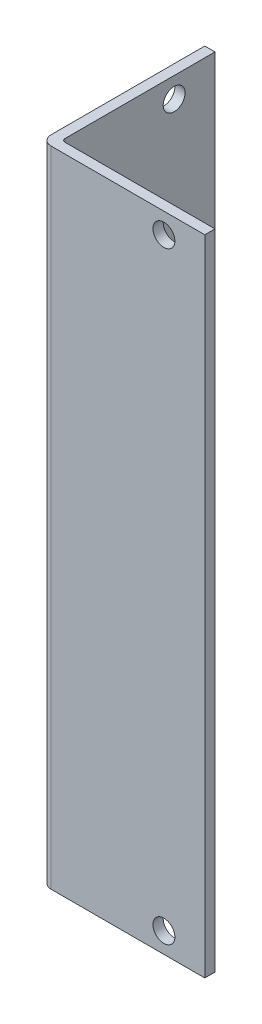
SolidWorks part; units mm, degrees
material "6061-T6 (SS)"
ref_plane "Front Plane" through (0, 0, 0) normal (0, 0, 1) x (1, 0, 0)
ref_plane "Top Plane" through (0, 0, 0) normal (0, 1, 0) x (1, 0, 0)
ref_plane "Right Plane" through (0, 0, 0) normal (1, 0, 0) x (0, 0, -1)
sketch "Sketch1" plane through (0, 0, 0) normal (0, 1, 0) x (1, 0, 0)
  line L1 (-12.7, -12.7) -> (12.7, -12.7)
  line L2 (-12.7, -12.7) -> (-12.7, 12.7)
  line L3 (-12.7, 12.7) -> (12.7, 12.7)
  line L4 (12.7, -12.7) -> (12.7, 12.7)
  line L5 (-12.7, -12.7) -> (12.7, 12.7) construction
  line L6 (-12.7, 12.7) -> (12.7, -12.7) construction
  point P0 (0, 0)
  dimension "D1" = 25.4
  dimension "D2" = 25.4
extrude "Boss-Extrude1" add sketch "Sketch1" along normal mid plane 113.5
sketch "Sketch2" plane through (0, 56.75, 0) normal (0, 1, 0) x (1, 0, 0)
  line L0 (-12.7, 12.7) -> (-12.7, -12.7) construction
  line L1 (12.7, 12.7) -> (-11.1125, 12.7)
  line L2 (12.7, 12.7) -> (12.7, -11.1125)
  line L3 (12.7, -11.1125) -> (-11.1125, -11.1125)
  line L4 (-11.1125, 12.7) -> (-11.1125, -11.1125)
  line L5 (-12.7, -12.7) -> (12.7, -12.7) construction
  dimension "D1" = 1.5875
  dimension "D2" = 1.5875
extrude "Cut-Extrude1" cut sketch "Sketch2" against normal through all
fillet "Fillet1" radius 0.508 1 edges at (-11.1125, 0, 11.1125)
hole_wizard "M3 Clearance Hole1" positions "Sketch3" profile "Sketch4" hole size "M3" standard "ANSI Metric" end condition through all
sketch "Sketch3" plane through (0, 0, 12.7) normal (0, 0, 1) x (1, 0, 0)
  line L1 (-12.7, 56.75) -> (12.7, 56.75) construction
  line L2 (12.7, 56.75) -> (12.7, -56.75) construction
  point P0 (6.35, 47.075)
  dimension "D1" = 6.35
  dimension "D2" = 9.675
sketch "Sketch4" plane through (6.35, 47.075, 12.7) normal (1, 0, 0) x (0, -1, 0)
  line L0 (0, 0) -> (0, 25.4)
  line L1 (0, 25.4) -> (1.7, 25.4)
  line L2 (1.7, 25.4) -> (1.7, 0)
  line L5 (1.7, 0) -> (0, 0)
  line L11 (0, -6.35) -> (0, 107.95) construction
  dimension "Thru Hole Dia." = 3.4
  dimension "Thru Hole Depth" = 25.4
hole_wizard "M3 Clearance Hole2" positions "Sketch5" profile "Sketch6" hole size "M3" standard "ANSI Metric" end condition through all
sketch "Sketch5" plane through (-12.7, 0, 0) normal (-1, 0, 0) x (0, 0, 1)
  line L1 (-12.7, 56.75) -> (12.7, 56.75) construction
  line L2 (-12.7, 56.75) -> (-12.7, -56.75) construction
  point P0 (-6.35, 47.075)
  dimension "D1" = 6.35
  dimension "D2" = 9.675
sketch "Sketch6" plane through (-12.7, 47.075, -6.35) normal (0, 1, 0) x (0, 0, 1)
  line L0 (0, 0) -> (0, 25.4)
  line L1 (0, 25.4) -> (1.7, 25.4)
  line L2 (1.7, 25.4) -> (1.7, 0)
  line L5 (1.7, 0) -> (0, 0)
  line L11 (0, -6.35) -> (0, 107.95) construction
  dimension "Thru Hole Dia." = 3.4
  dimension "Thru Hole Depth" = 25.4
hole_wizard "M3 Clearance Hole3" positions "Sketch7" profile "Sketch8" hole size "M3" standard "ANSI Metric" end condition through all
sketch "Sketch7" plane through (0, 0, 12.7) normal (0, 0, 1) x (1, 0, 0)
  line L2 (-12.7, -56.75) -> (12.7, -56.75) construction
  line L3 (12.7, 56.75) -> (12.7, -56.75) construction
  point P0 (6.35, -46.575)
  dimension "D1" = 6.35
  dimension "D2" = 10.175
sketch "Sketch8" plane through (6.35, -46.575, 12.7) normal (1, 0, 0) x (0, -1, 0)
  line L0 (0, 0) -> (0, 25.4)
  line L1 (0, 25.4) -> (1.7, 25.4)
  line L2 (1.7, 25.4) -> (1.7, 0)
  line L5 (1.7, 0) -> (0, 0)
  line L11 (0, -6.35) -> (0, 107.95) construction
  dimension "Thru Hole Dia." = 3.4
  dimension "Thru Hole Depth" = 25.4
hole_wizard "M3 Clearance Hole4" positions "Sketch9" profile "Sketch10" hole size "M3" standard "ANSI Metric" end condition through all
sketch "Sketch9" plane through (-12.7, 0, 0) normal (-1, 0, 0) x (0, 0, 1)
  line L1 (-12.7, -56.75) -> (12.7, -56.75) construction
  line L2 (-12.7, 56.75) -> (-12.7, -56.75) construction
  point P0 (-6.35, -46.575)
  dimension "D1" = 6.35
  dimension "D2" = 10.175
sketch "Sketch10" plane through (-12.7, -46.575, -6.35) normal (0, 1, 0) x (0, 0, 1)
  line L0 (0, 0) -> (0, 25.4)
  line L1 (0, 25.4) -> (1.7, 25.4)
  line L2 (1.7, 25.4) -> (1.7, 0)
  line L5 (1.7, 0) -> (0, 0)
  line L11 (0, -6.35) -> (0, 107.95) construction
  dimension "Thru Hole Dia." = 3.4
  dimension "Thru Hole Depth" = 25.4
fillet "Fillet2" radius 1.5 1 edges at (-12.7, 0, 12.7)
sketch "Sketch11" plane through (-12.7, 0, 0) normal (-1, 0, 0) x (0, 0, 1)
  line L0 (12.7, 56.75) -> (12.7, -56.75) construction
  line L1 (-12.7, 56.75) -> (4.2, 56.75)
  line L2 (-12.7, 56.75) -> (-12.7, 50.25)
  line L3 (-12.7, 50.25) -> (4.2, 50.25)
  line L4 (4.2, 56.75) -> (4.2, 50.25)
  line L6 (-12.7, -56.75) -> (4.2, -56.75)
  line L7 (-12.7, -56.75) -> (-12.7, -49.75)
  line L8 (-12.7, -49.75) -> (4.2, -49.75)
  line L9 (4.2, -56.75) -> (4.2, -49.75)
  dimension "D1" = 8.5
  dimension "D2" = 6.5
  dimension "D3" = 7
extrude "Cut-Extrude2" cut sketch "Sketch11" against normal up to next
sketch "Sketch12" plane through (0, 0, 12.7) normal (0, 0, 1) x (1, 0, 0)
  line L0 (-12.7, -56.75) -> (-12.7, 56.75) construction
  line L1 (12.7, 56.75) -> (-4.2, 56.75)
  line L2 (12.7, 56.75) -> (12.7, 50.25)
  line L3 (12.7, 50.25) -> (-4.2, 50.25)
  line L4 (-4.2, 56.75) -> (-4.2, 50.25)
  line L5 (12.7, -56.75) -> (-4.2, -56.75)
  line L6 (12.7, -56.75) -> (12.7, -49.75)
  line L7 (12.7, -49.75) -> (-4.2, -49.75)
  line L8 (-4.2, -56.75) -> (-4.2, -49.75)
  dimension "D1" = 8.5
  dimension "D2" = 7
  dimension "D3" = 8.5
  dimension "D4" = 6.5
extrude "Cut-Extrude3" cut sketch "Sketch12" against normal up to next
fillet "Fillet3" radius 3.81 4 edges at (-4.2, -49.75, 11.9062) (-11.9063, -49.75, 4.2) (-11.9063, 50.25, 4.2) (-4.2, 50.25, 11.9062)
sketch "Sketch13" plane through (-12.7, 0, 0) normal (-1, 0, 0) x (0, 0, 1)
  line L0 (4.2, -56.75) -> (4.2, 56.75) construction
  line L9 (2.7, -56.75) -> (2.7, 56.75) construction
  line L10 (-12.7, 50.25) -> (-12.7, -49.75) construction
  line L11 (2.7, -43.4) -> (-12.7, -43.4)
  line L12 (2.7, -43.4) -> (2.7, 43.9)
  line L13 (2.7, 43.9) -> (-12.7, 43.9)
  line L14 (-12.7, -43.4) -> (-12.7, 43.9)
  circle A2 centre (-6.35, 47.075) radius 1.7 construction
  circle A3 centre (-6.35, -46.575) radius 1.7 construction
  dimension "D2" = 3.175
  dimension "D3" = 3.175
  dimension "D1" = 1.5
extrude "Cut-Extrude4" cut sketch "Sketch13" against normal up to next
sketch "Sketch14" plane through (0, 0, 12.7) normal (0, 0, 1) x (1, 0, 0)
  line L0 (-4.2, 56.75) -> (-4.2, -56.75) construction
  line L1 (-2.7, 56.75) -> (-2.7, -56.75) construction
  line L2 (12.7, 50.25) -> (12.7, -49.75) construction
  line L3 (-2.7, -43.4) -> (12.7, -43.4)
  line L4 (-2.7, -43.4) -> (-2.7, 43.9)
  line L5 (-2.7, 43.9) -> (12.7, 43.9)
  line L6 (12.7, -43.4) -> (12.7, 43.9)
  circle A0 centre (6.35, 47.075) radius 1.7 construction
  circle A1 centre (6.35, -46.575) radius 1.7 construction
  dimension "D2" = 3.175
  dimension "D3" = 3.175
  dimension "D1" = 1.5
extrude "Cut-Extrude5" cut sketch "Sketch14" against normal up to next
chamfer "Chamfer2" distance 6.35 angle 45 4 edges at (-11.9063, 43.9, 2.7) (-2.7, 43.9, 11.9062) (-2.7, -43.4, 11.9062) (-11.9062, -43.4, 2.7)
fillet "Fillet5" radius 3.81 8 edges at (3.65, -43.4, 11.9062) (-2.7, -37.05, 11.9062) (-11.9063, -43.4, -3.65) (-11.9063, -37.05, 2.7) (-11.9063, 43.9, -3.65) (-11.9063, 37.55, 2.7) (-2.7, 37.55, 11.9062) (3.65, 43.9, 11.9062)
sketch "Sketch15" plane through (0, 56.75, 0) normal (0, 1, 0) x (1, 0, 0)
  line L0 (-11.2, -12.7) -> (-4.2, -12.7) construction
  line L1 (-12.7, -12.7) -> (-0.39, -12.7)
  line L2 (-12.7, -12.7) -> (-12.7, -0.39)
  line L3 (-12.7, -0.39) -> (-0.39, -0.39)
  line L4 (-0.39, -12.7) -> (-0.39, -0.39)
  line L5 (-12.7, -4.2) -> (-12.7, -11.2) construction
  line L6 (-0.39, -11.1125) -> (-0.39, -12.7) construction
extrude "Cut-Extrude6" cut sketch "Sketch15" against normal up to surface (6.5 mm away) up to face at (6.155, 50.25, 11.9062)
sketch "Sketch16" plane through (0, 50.25, 0) normal (0, 1, 0) x (1, 0, 0)
  line L0 (-11.2, -12.7) -> (12.7, -12.7) construction
  line L1 (-12.7, -12.7) -> (-5.7, -12.7)
  line L2 (-12.7, -12.7) -> (-12.7, -5.7)
  line L3 (-12.7, -5.7) -> (-5.7, -5.7)
  line L4 (-5.7, -12.7) -> (-5.7, -5.7)
  line L5 (-12.7, 12.7) -> (-12.7, -11.2) construction
  dimension "D1" = 7
  dimension "D2" = 7
sketch "Sketch17" plane through (0, -56.75, 0) normal (0, -1, 0) x (1, 0, 0)
  line L0 (-11.2, 12.7) -> (-4.2, 12.7) construction
  line L1 (-12.7, 12.7) -> (-0.39, 12.7)
  line L2 (-12.7, 12.7) -> (-12.7, 0.39)
  line L3 (-12.7, 0.39) -> (-0.39, 0.39)
  line L4 (-0.39, 12.7) -> (-0.39, 0.39)
  line L5 (-12.7, 4.2) -> (-12.7, 11.2) construction
  line L6 (-11.1125, 0.39) -> (-12.7, 0.39) construction
  line L7 (-0.39, 12.7) -> (-0.39, 11.1125) construction
extrude "Cut-Extrude8" cut sketch "Sketch17" against normal up to surface (7 mm away) up to face at (6.155, -49.75, 11.9062)
sketch "Sketch18" plane through (-12.7, 0, 0) normal (-1, 0, 0) x (0, 0, 1)
  line L0 (-12.7, -43.4) -> (-5.2282, -43.4) construction
  line L1 (5.7, -43.4) -> (11.2, -43.4)
  line L2 (5.7, -43.4) -> (5.7, -40.4)
  line L3 (5.7, -40.4) -> (11.2, -40.4)
  line L4 (11.2, -43.4) -> (11.2, -40.4)
  line L5 (12.7, 50.25) -> (12.7, -49.75) construction
  point P8 (8.45, -40.4)
  dimension "D1" = 5.5
  dimension "D2" = 3
  dimension "D3" = 4.25
sketch "Sketch19" plane through (0, -49.75, 0) normal (0, -1, 0) x (1, 0, 0)
  line L0 (12.7, 12.7) -> (-11.2, 12.7) construction
  line L1 (-12.7, 5.7) -> (-5.7, 5.7)
  line L2 (-12.7, 5.7) -> (-12.7, 12.7)
  line L3 (-12.7, 12.7) -> (-5.7, 12.7)
  line L4 (-5.7, 5.7) -> (-5.7, 12.7)
  line L5 (-12.7, 11.2) -> (-12.7, -12.7) construction
sketch "Sketch20" plane through (-12.7, 0, 0) normal (-1, 0, 0) x (0, 0, 1)
  line L0 (-12.7, 43.9) -> (-12.7, -43.4)
  line L14 (11.2, -49.75) -> (11.2, 50.25)
  line L15 (11.2, 50.25) -> (-12.7, 50.25)
  line L16 (-12.7, 50.25) -> (-12.7, 43.9)
  line L17 (-12.7, 43.9) -> (-5.2282, 43.9)
  line L18 (-2.5341, 42.7841) -> (1.5841, 38.6659)
  line L19 (2.7, 35.9718) -> (2.7, -35.4718)
  line L20 (1.5841, -38.1659) -> (-2.5341, -42.2841)
  line L21 (-5.2282, -43.4) -> (-12.7, -43.4)
  line L22 (-12.7, -43.4) -> (-12.7, -49.75)
  line L23 (-12.7, -49.75) -> (11.2, -49.75)
  line L27 (11.2, -49.75) -> (11.2, 50.25)
  line L28 (11.2, 50.25) -> (-12.7, 50.25)
  line L29 (-12.7, 50.25) -> (-12.7, 43.9)
  line L30 (-12.7, 43.9) -> (-5.2282, 43.9)
  line L31 (-2.5341, 42.7841) -> (1.5841, 38.6659)
  line L32 (2.7, 35.9718) -> (2.7, -35.4718)
  line L33 (1.5841, -38.1659) -> (-2.5341, -42.2841)
  line L34 (-5.2282, -43.4) -> (-12.7, -43.4)
  line L35 (-12.7, -43.4) -> (-12.7, -49.75)
  line L36 (-12.7, -49.75) -> (11.2, -49.75)
  arc A6 (-2.5341, 42.7841) -> (-5.2282, 43.9) centre (-5.2282, 40.09) ccw
  arc A7 (2.7, 35.9718) -> (1.5841, 38.6659) centre (-1.11, 35.9718) ccw
  arc A8 (1.5841, -38.1659) -> (2.7, -35.4718) centre (-1.11, -35.4718) ccw
  arc A9 (-5.2282, -43.4) -> (-2.5341, -42.2841) centre (-5.2282, -39.59) ccw
  arc A11 (-2.5341, 42.7841) -> (-5.2282, 43.9) centre (-5.2282, 40.09) ccw
  arc A12 (2.7, 35.9718) -> (1.5841, 38.6659) centre (-1.11, 35.9718) ccw
  arc A13 (1.5841, -38.1659) -> (2.7, -35.4718) centre (-1.11, -35.4718) ccw
  arc A14 (-5.2282, -43.4) -> (-2.5341, -42.2841) centre (-5.2282, -39.59) ccw
  line M26 (-12.7, 43.9) -> (-5.2282, 43.9)
  arc M27 (-5.2282, 43.9) -> (-2.5341, 42.7841) centre (-5.2282, 40.09) cw
  line M28 (-2.5341, 42.7841) -> (1.5841, 38.6659)
  arc M29 (1.5841, 38.6659) -> (2.7, 35.9718) centre (-1.11, 35.9718) cw
  line M30 (2.7, 35.9718) -> (2.7, -35.4718)
  arc M31 (2.7, -35.4718) -> (1.5841, -38.1659) centre (-1.11, -35.4718) cw
  line M32 (1.5841, -38.1659) -> (-2.5341, -42.2841)
  arc M33 (-2.5341, -42.2841) -> (-5.2282, -43.4) centre (-5.2282, -39.59) cw
  line M34 (-5.2282, -43.4) -> (-12.7, -43.4)
  dimension "D1" = 0
extrude "Boss-Extrude2" add sketch "Sketch20" against normal up to surface (1.5875 mm away) contours L0 M26 M34 M33 M32 M31 M30 M29 M28 M27 region at (-12.7, 0.25, -5.177) up to face at (-11.1125, -46.575, -4.65)
sketch "Sketch21" plane through (0, 0, 12.7) normal (0, 0, 1) x (1, 0, 0)
  line L0 (12.7, 43.9) -> (12.7, -43.4)
  line L14 (-11.2, 50.25) -> (-11.2, -49.75)
  line L15 (-11.2, -49.75) -> (12.7, -49.75)
  line L16 (12.7, -49.75) -> (12.7, -43.4)
  line L17 (12.7, -43.4) -> (5.2282, -43.4)
  line L18 (2.5341, -42.2841) -> (-1.5841, -38.1659)
  line L19 (-2.7, -35.4718) -> (-2.7, 35.9718)
  line L20 (-1.5841, 38.6659) -> (2.5341, 42.7841)
  line L21 (5.2282, 43.9) -> (12.7, 43.9)
  line L22 (12.7, 43.9) -> (12.7, 50.25)
  line L23 (12.7, 50.25) -> (-11.2, 50.25)
  line L27 (-11.2, 50.25) -> (-11.2, -49.75)
  line L28 (-11.2, -49.75) -> (12.7, -49.75)
  line L29 (12.7, -49.75) -> (12.7, -43.4)
  line L30 (12.7, -43.4) -> (5.2282, -43.4)
  line L31 (2.5341, -42.2841) -> (-1.5841, -38.1659)
  line L32 (-2.7, -35.4718) -> (-2.7, 35.9718)
  line L33 (-1.5841, 38.6659) -> (2.5341, 42.7841)
  line L34 (5.2282, 43.9) -> (12.7, 43.9)
  line L35 (12.7, 43.9) -> (12.7, 50.25)
  line L36 (12.7, 50.25) -> (-11.2, 50.25)
  arc A6 (2.5341, -42.2841) -> (5.2282, -43.4) centre (5.2282, -39.59) ccw
  arc A7 (-2.7, -35.4718) -> (-1.5841, -38.1659) centre (1.11, -35.4718) ccw
  arc A8 (-1.5841, 38.6659) -> (-2.7, 35.9718) centre (1.11, 35.9718) ccw
  arc A9 (5.2282, 43.9) -> (2.5341, 42.7841) centre (5.2282, 40.09) ccw
  arc A11 (2.5341, -42.2841) -> (5.2282, -43.4) centre (5.2282, -39.59) ccw
  arc A12 (-2.7, -35.4718) -> (-1.5841, -38.1659) centre (1.11, -35.4718) ccw
  arc A13 (-1.5841, 38.6659) -> (-2.7, 35.9718) centre (1.11, 35.9718) ccw
  arc A14 (5.2282, 43.9) -> (2.5341, 42.7841) centre (5.2282, 40.09) ccw
  line M24 (12.7, -43.4) -> (5.2282, -43.4)
  arc M25 (5.2282, -43.4) -> (2.5341, -42.2841) centre (5.2282, -39.59) cw
  line M26 (2.5341, -42.2841) -> (-1.5841, -38.1659)
  arc M27 (-1.5841, -38.1659) -> (-2.7, -35.4718) centre (1.11, -35.4718) cw
  line M28 (-2.7, -35.4718) -> (-2.7, 35.9718)
  arc M29 (-2.7, 35.9718) -> (-1.5841, 38.6659) centre (1.11, 35.9718) cw
  line M30 (-1.5841, 38.6659) -> (2.5341, 42.7841)
  arc M31 (2.5341, 42.7841) -> (5.2282, 43.9) centre (5.2282, 40.09) cw
  line M32 (5.2282, 43.9) -> (12.7, 43.9)
  dimension "D1" = 0
extrude "Boss-Extrude3" add sketch "Sketch21" against normal up to surface (1.5875 mm away) contours L0 M32 M31 M30 M29 M28 M27 M26 M25 M24 region at (5.177, 0.25, 12.7) up to face at (8.05, -46.575, 11.1125)
sketch "Sketch23" plane through (-11.1125, 0, 0) normal (1, 0, 0) x (0, 0, -1)
  line L0 (-220.6296, -34.1208) -> (-227.7171, -34.1208)
  line L1 (-220.6296, -34.1208) -> (-220.6296, -41.1208)
  line L2 (-220.6296, -41.1208) -> (-227.7171, -41.1208)
  line L3 (-227.7171, -34.1208) -> (-227.7171, -41.1208)
  line L4 (-11.1125, -49.75) -> (-11.1125, 50.25) construction
  line L5 (-9.1125, 41.25) -> (-2.6125, 41.25)
  line L6 (-9.1125, 41.25) -> (-9.1125, 34.25)
  line L7 (-9.1125, 34.25) -> (-2.6125, 34.25)
  line L8 (-2.6125, 41.25) -> (-2.6125, 34.25)
  line L9 (-10.6045, 50.25) -> (12.7, 50.25) construction
  dimension "D1" = 8.5
  dimension "D2" = 2
  dimension "D3" = 9
  dimension "D4" = 16
extrude "Cut-Extrude12" cut sketch "Sketch23" against normal up to next contours L8 L7 L6 L5
fillet "Fillet9" radius 1.5875 4 edges at (-11.9063, 34.25, 2.6125) (-11.9063, 41.25, 2.6125) (-11.9062, 41.25, 9.1125) (-11.9062, 34.25, 9.1125)
